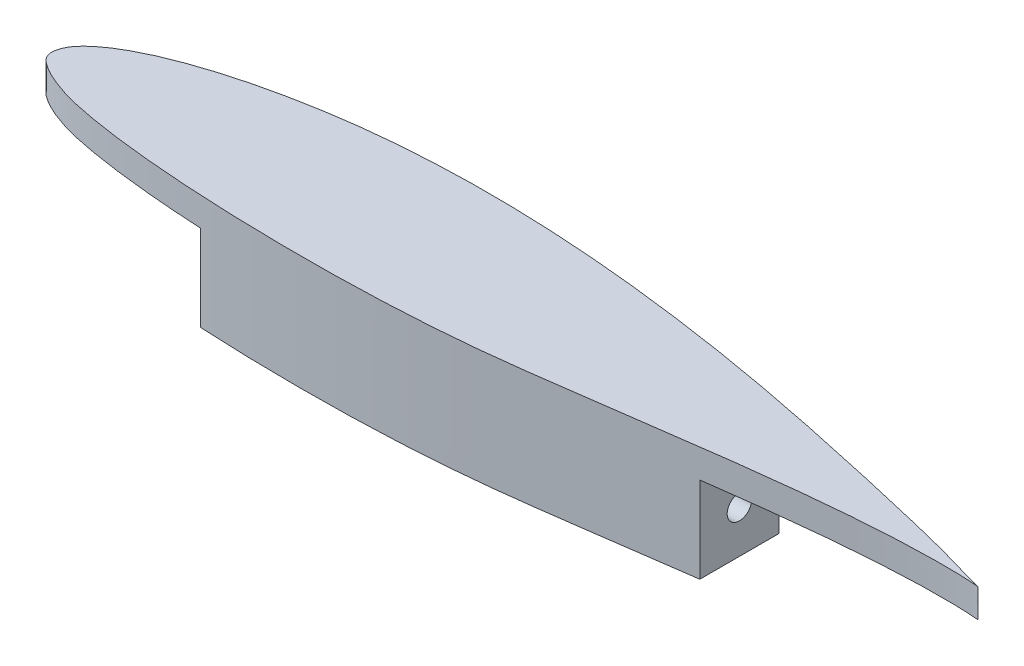
SolidWorks part; units mm, degrees
material "6061-T6 (SS)"
ref_plane "XY" through (0, 0, 0) normal (0, 0, 1) x (1, 0, 0)
ref_plane "XZ" through (0, 0, 0) normal (0, 1, 0) x (1, 0, 0)
ref_plane "YZ" through (0, 0, 0) normal (1, 0, 0) x (0, 0, -1)
ref_axis "X" through (-5.1769, 0, 0) along (1, 0, 0)
ref_axis "Y" through (0, -0.635, 0) along (0, 1, 0)
ref_axis "Z" through (0, 0, 6.6111) along (0, 0, -1)
curve "Curve1"
  spline degree 3 poles (995.3569, 0, -0.5432) (1001.155, 0, 0.1879) (995.5718, 0, -0.9246) (991.2494, 0, -2.2879) (981.0446, 0, -5.0877) (968.9498, 0, -8.7262) (953.5274, 0, -13.127) (935.5134, 0, -17.9449) (914.7445, 0, -23.0883) (891.4402, 0, -28.6534) (865.7805, 0, -34.6459) (838.0019, 0, -40.9657) (808.3517, 0, -47.5309) (777.096, 0, -54.2827) (744.4946, 0, -61.0639) (710.7715, 0, -67.7258) (676.0995, 0, -74.0606) (640.6784, 0, -80.0371) (604.6949, 0, -85.5293) (568.3525, 0, -90.423) (531.8502, 0, -94.7332) (495.3568, 0, -98.272) (459.0726, 0, -101.012) (423.1715, 0, -102.9337) (387.8102, 0, -103.9229) (353.1514, 0, -104.0237) (319.3396, 0, -103.1726) (286.5359, 0, -101.3432) (254.8576, 0, -98.6417) (224.4281, 0, -95.0237) (195.3708, 0, -90.5044) (167.7934, 0, -85.3182) (141.8565, 0, -79.4854) (117.7049, 0, -73.1484) (95.4935, 0, -66.3349) (75.3539, 0, -59.1445) (57.3891, 0, -51.6889) (41.7311, 0, -43.9701) (28.4493, 0, -36.1612) (17.5963, 0, -28.3521) (9.3066, 0, -20.5271) (3.4766, 0, -12.7057) (0.4861, 0, -4.9141) (-0.3806, 0, 2.591) (2.7525, 0, 9.7016) (9.6639, 0, 15.1532) (18.8474, 0, 20.8219) (30.9031, 0, 26.2644) (45.4992, 0, 31.4896) (62.7956, 0, 36.0423) (82.7299, 0, 39.9835) (105.2038, 0, 43.6037) (130.0965, 0, 46.7552) (157.1977, 0, 49.537) (186.3329, 0, 51.8585) (217.2991, 0, 53.7279) (249.8869, 0, 55.14) (283.8783, 0, 56.0382) (319.0392, 0, 56.4135) (355.1379, 0, 56.2373) (391.9546, 0, 55.3884) (429.301, 0, 53.8371) (466.9868, 0, 51.4625) (504.9446, 0, 48.178) (543.1768, 0, 43.7625) (581.7242, 0, 38.6673) (620.4685, 0, 33.2537) (659.1167, 0, 27.7301) (697.3646, 0, 22.3165) (734.8767, 0, 17.1793) (771.299, 0, 12.4954) (806.2647, 0, 8.3936) (839.3944, 0, 4.9528) (870.3106, 0, 2.262) (898.6262, 0, 0.2969) (924.0102, 0, -0.9442) (946.0427, 0, -1.5456) (964.7085, 0, -1.5976) (978.9866, 0, -1.3786) (990.5753, 0, -0.7024) (995.3569, 0, -0.5432) (1001.155, 0, 0.1879) (995.5718, 0, -0.9246) knots -0.009436 -0.004233 -0.001065 0 0.001057 0.004097 0.008898 0.01526 0.023019 0.032102 0.042513 0.054199 0.067048 0.080936 0.095743 0.111332 0.127567 0.144302 0.161459 0.178963 0.196684 0.214537 0.232436 0.25028 0.268 0.285494 0.302704 0.319581 0.336031 0.352019 0.367485 0.382387 0.396696 0.410359 0.423299 0.435455 0.446762 0.457168 0.466628 0.475111 0.482604 0.489076 0.494562 0.499184 0.503152 0.506644 0.509898 0.513968 0.519249 0.525671 0.533191 0.541845 0.551721 0.562815 0.575034 0.588306 0.602541 0.617652 0.633543 0.650105 0.667235 0.684817 0.702744 0.720935 0.739322 0.757805 0.776488 0.795439 0.814506 0.833536 0.852372 0.870837 0.888749 0.905922 0.922175 0.937319 0.951171 0.963571 0.974352 0.983388 0.990564 0.995767 0.998935 1 1.001057 1.004097 1.008898 periodic
sketch "Sketch2" plane through (0, 0, 0) normal (0, 1, 0) x (1, 0, 0)
  line L0 (0, 0) -> (102.6, 0) construction
  spline S1 degree 3 poles (102.1236, 0.0557) (102.7185, -0.0193) (102.1457, 0.0949) (101.7022, 0.2347) (100.6552, 0.522) (99.4142, 0.8953) (97.8319, 1.3468) (95.9837, 1.8411) (93.8528, 2.3689) (91.4618, 2.9398) (88.8291, 3.5547) (85.979, 4.2031) (82.9369, 4.8767) (79.7301, 5.5694) (76.3851, 6.2652) (72.9252, 6.9487) (69.3678, 7.5986) (65.7336, 8.2118) (62.0417, 8.7753) (58.313, 9.2774) (54.5678, 9.7196) (50.8236, 10.0827) (47.1009, 10.3638) (43.4174, 10.561) (39.7893, 10.6625) (36.2333, 10.6728) (32.7642, 10.5855) (29.3986, 10.3978) (26.1484, 10.1206) (23.0263, 9.7494) (20.045, 9.2858) (17.2156, 8.7536) (14.5545, 8.1552) (12.0765, 7.505) (9.7976, 6.806) (7.7313, 6.0682) (5.8881, 5.3033) (4.2816, 4.5113) (2.9189, 3.7101) (1.8054, 2.9089) (0.9549, 2.1061) (0.3567, 1.3036) (0.0499, 0.5042) (-0.0391, -0.2658) (0.2824, -0.9954) (0.9915, -1.5547) (1.9337, -2.1363) (3.1707, -2.6947) (4.6682, -3.2308) (6.4428, -3.6979) (8.4881, -4.1023) (10.7939, -4.4737) (13.3479, -4.7971) (16.1285, -5.0825) (19.1178, -5.3207) (22.2949, -5.5125) (25.6384, -5.6574) (29.1259, -5.7495) (32.7334, -5.788) (36.4371, -5.77) (40.2145, -5.6829) (44.0463, -5.5237) (47.9128, -5.2801) (51.8073, -4.9431) (55.7299, -4.49) (59.6849, -3.9673) (63.6601, -3.4118) (67.6254, -2.8451) (71.5496, -2.2897) (75.3983, -1.7626) (79.1353, -1.282) (82.7228, -0.8612) (86.1219, -0.5082) (89.2939, -0.2321) (92.1991, -0.0305) (94.8034, 0.0969) (97.064, 0.1586) (98.9791, 0.1639) (100.444, 0.1414) (101.633, 0.0721) (102.1236, 0.0557) (102.7185, -0.0193) (102.1457, 0.0949) knots -0.009436 -0.004233 -0.001065 0 0.001057 0.004097 0.008898 0.01526 0.023019 0.032102 0.042513 0.054199 0.067048 0.080936 0.095743 0.111332 0.127567 0.144302 0.161459 0.178963 0.196684 0.214537 0.232436 0.25028 0.268 0.285494 0.302704 0.319581 0.336031 0.352019 0.367485 0.382387 0.396696 0.410359 0.423299 0.435455 0.446762 0.457168 0.466628 0.475111 0.482604 0.489076 0.494562 0.499184 0.503152 0.506644 0.509898 0.513968 0.519249 0.525671 0.533191 0.541845 0.551721 0.562815 0.575034 0.588306 0.602541 0.617652 0.633543 0.650105 0.667235 0.684817 0.702744 0.720935 0.739322 0.757805 0.776488 0.795439 0.814506 0.833536 0.852372 0.870837 0.888749 0.905922 0.922175 0.937319 0.951171 0.963571 0.974352 0.983388 0.990564 0.995767 0.998935 1 1.001057 1.004097 1.008898 only from (102.6, 0) to (102.6, 0)
  dimension "D1" = 102.6
extrude "Boss-Extrude1" add sketch "Sketch2" along normal blind 12.7
sketch "Sketch4" plane through (0, 0, 0) normal (0, -1, 0) x (1, 0, 0)
  line L0 (0, 0) -> (102.6, 0) construction
  line L1 (73.775, -10.6642) -> (21.95, -10.6642)
  line L2 (73.775, -10.6642) -> (73.775, 10.6642)
  line L3 (73.775, 10.6642) -> (21.95, 10.6642)
  line L4 (21.95, -10.6642) -> (21.95, 10.6642)
  spline S0 degree 3 poles (102.1457, -0.0949) (102.7185, 0.0193) (102.1236, -0.0557) (101.633, -0.0721) (100.444, -0.1414) (98.9791, -0.1639) (97.064, -0.1586) (94.8034, -0.0969) (92.1991, 0.0305) (89.2939, 0.2321) (86.1219, 0.5082) (82.7228, 0.8612) (79.1353, 1.282) (75.3983, 1.7626) (71.5496, 2.2897) (67.6254, 2.8451) (63.6601, 3.4118) (59.6849, 3.9673) (55.7299, 4.49) (51.8073, 4.9431) (47.9128, 5.2801) (44.0463, 5.5237) (40.2145, 5.6829) (36.4371, 5.77) (32.7334, 5.788) (29.1259, 5.7495) (25.6384, 5.6574) (22.2949, 5.5125) (19.1178, 5.3207) (16.1285, 5.0825) (13.3479, 4.7971) (10.7939, 4.4737) (8.4881, 4.1023) (6.4428, 3.6979) (4.6682, 3.2308) (3.1707, 2.6947) (1.9337, 2.1363) (0.9915, 1.5547) (0.2824, 0.9954) (-0.0391, 0.2658) (0.0499, -0.5042) (0.3567, -1.3036) (0.9549, -2.1061) (1.8054, -2.9089) (2.9189, -3.7101) (4.2816, -4.5113) (5.8881, -5.3033) (7.7313, -6.0682) (9.7976, -6.806) (12.0765, -7.505) (14.5545, -8.1552) (17.2156, -8.7536) (20.045, -9.2858) (23.0263, -9.7494) (26.1484, -10.1206) (29.3986, -10.3978) (32.7642, -10.5855) (36.2333, -10.6728) (39.7893, -10.6625) (43.4174, -10.561) (47.1009, -10.3638) (50.8236, -10.0827) (54.5678, -9.7196) (58.313, -9.2774) (62.0417, -8.7753) (65.7336, -8.2118) (69.3678, -7.5986) (72.9252, -6.9487) (76.3851, -6.2652) (79.7301, -5.5694) (82.9369, -4.8767) (85.979, -4.2031) (88.8291, -3.5547) (91.4618, -2.9398) (93.8528, -2.3689) (95.9837, -1.8411) (97.8319, -1.3468) (99.4142, -0.8953) (100.6552, -0.522) (101.7022, -0.2347) (102.1457, -0.0949) (102.7185, 0.0193) (102.1236, -0.0557) knots -0.008898 -0.004097 -0.001057 0 0.001065 0.004233 0.009436 0.016612 0.025648 0.036429 0.048829 0.062681 0.077825 0.094078 0.111251 0.129163 0.147628 0.166464 0.185494 0.204561 0.223512 0.242195 0.260678 0.279065 0.297256 0.315183 0.332765 0.349895 0.366457 0.382348 0.397459 0.411694 0.424966 0.437185 0.448279 0.458155 0.466809 0.474329 0.480751 0.486032 0.490102 0.493356 0.496848 0.500816 0.505438 0.510924 0.517396 0.524889 0.533372 0.542832 0.553238 0.564545 0.576701 0.589641 0.603304 0.617613 0.632515 0.647981 0.663969 0.680419 0.697296 0.714506 0.732 0.74972 0.767564 0.785463 0.803316 0.821037 0.838541 0.855698 0.872433 0.888668 0.904257 0.919064 0.932952 0.945801 0.957487 0.967898 0.976981 0.98474 0.991102 0.995903 0.998943 1 1.001065 1.004233 1.009436 only from (102.6, 0) to (102.6, 0) construction
  point P8 (21.95, 0)
  dimension "D1" = 102.6
  dimension "D2" = 28.825
  dimension "D3" = 51.825
extrude "Cut-Extrude1" cut sketch "Sketch4" against normal blind 9.525 flip side to cut
hole_wizard "#6-32 Tapped Hole1" positions "Sketch5" profile "Sketch7" tap size "#6-32" standard "ANSI Inch"
sketch "Sketch5" plane through (73.775, 0, 0) normal (1, 0, 0) x (0, 0, -1)
  line L0 (2.3954, 9.525) -> (2.3954, 0)
  line L1 (6.7769, 9.525) -> (-1.9861, 9.525) construction
  line L2 (6.7769, 0) -> (-1.9861, 0) construction
  point P0 (2.3954, 4.7625)
sketch "Sketch7" plane through (73.775, 4.7625, -2.3954) normal (0, 1, 0) x (0, 0, -1)
  line L0 (0, 0) -> (0, 10.8127)
  line L1 (0, 10.8127) -> (1.3525, 10)
  line L2 (1.3525, 10) -> (1.3525, 0)
  line L5 (1.3525, 0) -> (0, 0)
  line L10 (0, 10.8127) -> (-1.3525, 10) construction
  line L11 (0, -6.35) -> (0, 107.95) construction
  dimension "Tap Drill Dia." = 2.7051
  dimension "Tap Drill Depth" = 10
  dimension "Drill Angle" = 118
cosmetic thread "Hole Thread1" parameters "D1"=10, "D2"=3.5052
hole_wizard "#6-32 Tapped Hole2" positions "Sketch8" profile "Sketch9" tap size "#6-32" standard "ANSI Inch"
sketch "Sketch8" plane through (21.95, 0, 0) normal (-1, 0, 0) x (0, 0, 1)
  line L0 (-2.5283, 0) -> (-2.5283, 9.525) construction
  line L4 (5.485, 0) -> (5.485, 9.525) construction
  line L5 (5.485, 0) -> (-9.5763, 0) construction
  line L6 (5.485, 9.525) -> (-9.5763, 9.525) construction
  point P0 (-2.5283, 4.7625)
  dimension "D1" = 8.0133
sketch "Sketch9" plane through (21.95, 4.7625, -2.5283) normal (0, 1, 0) x (0, 0, 1)
  line L0 (0, 0) -> (0, 10.8127)
  line L1 (0, 10.8127) -> (1.3525, 10)
  line L2 (1.3525, 10) -> (1.3525, 0)
  line L5 (1.3525, 0) -> (0, 0)
  line L10 (0, 10.8127) -> (-1.3525, 10) construction
  line L11 (0, -6.35) -> (0, 107.95) construction
  dimension "Tap Drill Dia." = 2.7051
  dimension "Tap Drill Depth" = 10
  dimension "Drill Angle" = 118
cosmetic thread "Hole Thread3" parameters "D1"=10, "D2"=3.7051
equation "\"D2@Sketch4\"=\"D1@Sketch4\"*.25+.125in"
